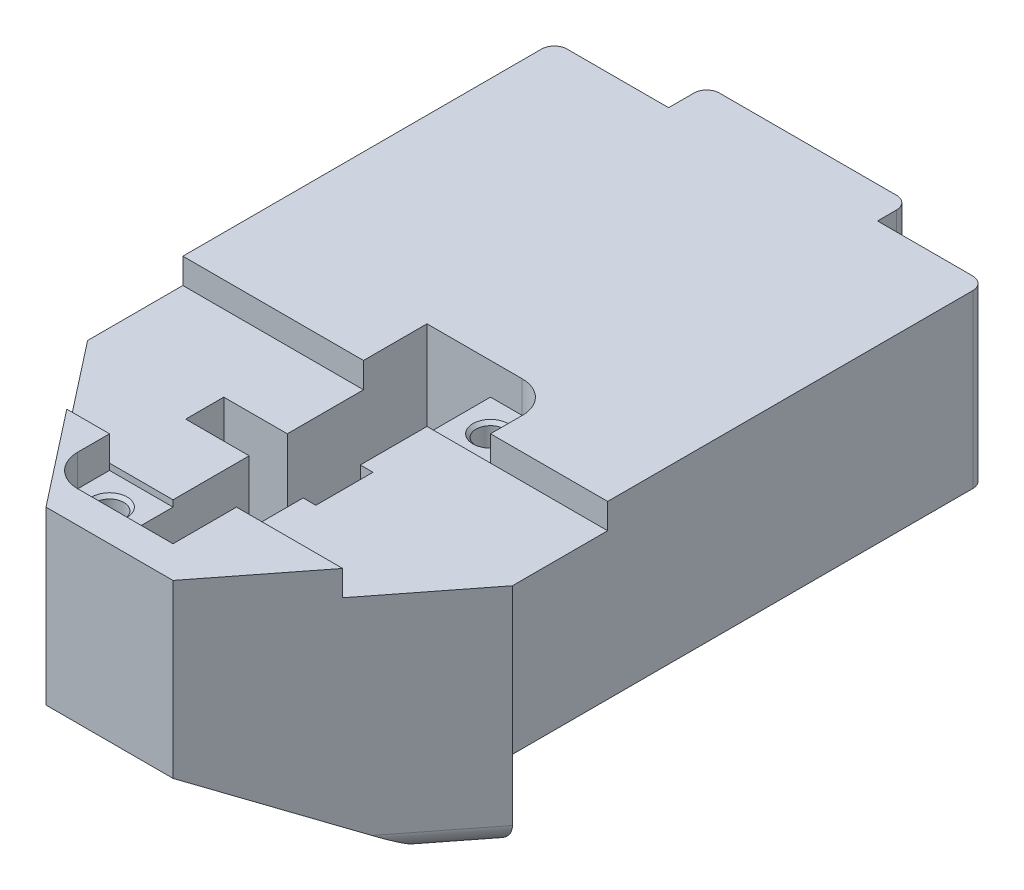
SolidWorks part; units mm, degrees
ref_plane "Front Plane" through (0, 0, 0) normal (0, 0, 1) x (1, 0, 0)
ref_plane "Top Plane" through (0, 0, 0) normal (0, 1, 0) x (1, 0, 0)
ref_plane "Right Plane" through (0, 0, 0) normal (1, 0, 0) x (0, 0, -1)
sketch "Sketch1" plane through (0, 0, 0) normal (0, 1, 0) x (1, 0, 0)
  line L0 (0, 0) -> (-16.35, 0)
  line L1 (-16.35, 0) -> (-16.35, -9.85)
  line L2 (-16.35, -9.85) -> (-2.6, -9.85)
  line L3 (-20.1, -33) -> (-20.1, -75)
  line L4 (-20.1, -75) -> (0, -75)
  line L5 (0, -75) -> (0, 0)
  line L6 (-2.6, -9.85) -> (-2.6, -33)
  line L7 (-2.6, -33) -> (-20.1, -33)
  dimension "D1" = 16.35
  dimension "D2" = 9.85
  dimension "D3" = 13.75
  dimension "D4" = 3.75
  dimension "D5" = 23.15
  dimension "D6" = 42
extrude "Boss-Extrude1" add sketch "Sketch1" along normal blind 7.7
sketch "Sketch2" plane through (0, 0, 75) normal (0, 0, 1) x (1, 0, 0)
  line L0 (-20.1, 7.7) -> (-20.1, 0) construction
  line L1 (-20.1, 5.1) -> (-13.1, 5.1)
  line L2 (-20.1, 5.1) -> (-20.1, 2)
  line L3 (-20.1, 2) -> (-13.1, 2)
  line L4 (-13.1, 5.1) -> (-13.1, 2)
  line L5 (-20.1, 0) -> (0, 0) construction
  dimension "D1" = 7
  dimension "D2" = 3.1
  dimension "D3" = 2
extrude "Cut-Extrude1" cut sketch "Sketch2" against normal through all
fillet "Fillet1" radius 10 1 edges at (-2.6, 3.85, 33)
sketch "Sketch3" plane through (0, 7.7, 0) normal (0, 1, 0) x (1, 0, 0)
  line L0 (0, 0) -> (0, -75)
  line L1 (0, -75) -> (-33.45, -75)
  line L2 (-33.45, -75) -> (-33.45, 0)
  line L3 (-33.45, 0) -> (0, 0)
  line L4 (0, -75) -> (0, -105)
  line L5 (0, -105) -> (-10, -105)
  line L6 (0, 0) -> (0, 4.5)
  line L7 (-33.45, -75) -> (-10, -105)
  line L8 (0, 4.5) -> (-33.45, 4.5)
  line L9 (-33.45, 4.5) -> (-33.45, 0)
  line M7 (0, -75) -> (0, 0)
  line M8 (0, 0) -> (-16.35, 0)
  line M9 (-16.35, 0) -> (-16.35, -9.85)
  line M10 (-16.35, -9.85) -> (-2.6, -9.85)
  line M11 (-2.6, -9.85) -> (-2.6, -23)
  arc M12 (-2.6, -23) -> (-12.6, -33) centre (-12.6, -23) cw
  line M13 (-12.6, -33) -> (-20.1, -33)
  line M14 (-20.1, -33) -> (-20.1, -75)
  line M15 (-20.1, -75) -> (0, -75)
  dimension "D1" = 33.45
  dimension "D2" = 30
  dimension "D3" = 10
  dimension "D4" = 4.5
extrude "Boss-Extrude2" add sketch "Sketch3" along normal blind 2 contours M15 M7 M8 M9 M10 M11 M12 M13 M14 | L3 L2 L1 M14 M13 M12 M11 M10 M9 | L5 L4 L1 M15 | L3 M8 region at (-9.1846, 7.7, 44.4658) region at (-16.725, 7.7, -2.25) region at (-11.9172, 7.7, 87.3015) region at (-22.489, 7.7, 32.1752)
sketch "Sketch4" plane through (0, 0, 0) normal (1, 0, 0) x (0, 0, -1)
  line L0 (-105, 9.7) -> (-105, 34.7)
  line L1 (-105, 34.7) -> (4.5, 34.7)
  line L4 (-105, 9.7) -> (4.5, 9.7)
  line L5 (4.5, 9.7) -> (4.5, 34.7)
  dimension "D2" = 25
extrude "Boss-Extrude3" add sketch "Sketch4" against normal up to surface (33.45 mm away) up to face at (-33.45, 8.7, 35.25)
sketch "Sketch5" plane through (-33.45, 0, 0) normal (-1, 0, 0) x (0, 0, 1)
  line L0 (75, 7.7) -> (75, -5)
  line L1 (75, -5) -> (82, -5)
  line L2 (82, -5) -> (105, 7.7)
  line L3 (105, 7.7) -> (75, 7.7)
  line L4 (33, 0) -> (75, 0) construction
  dimension "D1" = 5
  dimension "D2" = 7
extrude "Boss-Extrude4" add sketch "Sketch5" against normal up to surface (33.45 mm away) up to face at (0, 12.525, 43.875)
sketch "Sketch6" plane through (0, 7.7, 0) normal (0, 1, 0) x (1, 0, 0)
  line L0 (-33.45, -75) -> (-10, -105)
  line L1 (-10, -105) -> (-33.45, -105)
  line L2 (-33.45, -105) -> (-33.45, -75)
extrude "Cut-Extrude2" cut sketch "Sketch6" against normal through all both and the other way through all
sketch "Sketch7" plane through (0, 0, 0) normal (1, 0, 0) x (0, 0, -1)
  line L0 (-75, 0) -> (-85, 0)
  line L1 (-85, 0) -> (-80, -5)
  line L2 (-82, -5) -> (-75, -5) construction
  line L3 (-80, -5) -> (-75, -5)
  line L4 (-75, -5) -> (-75, 0)
  dimension "D1" = 5
  dimension "D2" = 10
extrude "Cut-Extrude3" cut sketch "Sketch7" against normal blind 10
fillet "Fillet3" radius 1 2 edges at (-5, -5, 80) (-10, -5, 77.5)
fillet "Fillet4" [suppressed] radius 5
sketch "Sketch9" plane through (0, 0, 0) normal (1, 0, 0) x (0, 0, -1)
  line L4 (4.5, 34.7) -> (-105, 34.7) construction
  line L5 (-90, 34.7) -> (-60, 34.7)
  line L6 (-90, 34.7) -> (-90, 30.7)
  line L7 (-90, 30.7) -> (-60, 30.7)
  line L8 (-60, 34.7) -> (-60, 30.7)
  line L9 (-105, 34.7) -> (-105, 7.7) construction
  dimension "D1" = 4
  dimension "D2" = 30
  dimension "D3" = 15
extrude "Cut-Extrude5" cut sketch "Sketch9" against normal up to next
mirror "Mirror1" about plane through (0, 7.7, 75) normal (-1, 0, 0) of bodies 113 110
fillet "Fillet5" radius 3 2 edges at (-30.7142, -5, 78.5) (30.7142, -5, 78.5)
sketch "Sketch8" plane through (0, 34.7, 0) normal (0, 1, 0) x (1, 0, 0)
  line L0 (33.45, 4.5) -> (33.45, -0.5)
  line L2 (33.45, -0.5) -> (16.45, -0.5)
  line L3 (16.45, -0.5) -> (16.45, 4.5)
  line L5 (16.45, 4.5) -> (33.45, 4.5)
  line L6 (0, 37.0905) -> (0, -37.0905) construction
  line L7 (-16.45, -0.5) -> (-16.45, 4.5) construction
  line L8 (-33.45, -0.5) -> (-16.45, -0.5) construction
  line L9 (-33.45, 4.5) -> (-33.45, -0.5) construction
  line L10 (-16.45, 4.5) -> (-33.45, 4.5) construction
  line L11 (-15.45, -1.5) -> (-15.45, 5.5)
  line L12 (-15.45, 5.5) -> (-34.45, 5.5)
  line L13 (-34.45, 5.5) -> (-34.45, -1.5)
  line L14 (-34.45, -1.5) -> (-15.45, -1.5)
  line L15 (33.45, 4.5) -> (33.45, -60) construction
  point P2 (33.45, 4.5)
  point P3 (33.45, -0.5)
  point P13 (0, 0)
  dimension "D1" = 5
  dimension "D2" = 17
  dimension "D3" = 1
extrude "Cut-Extrude4" cut sketch "Sketch8" against normal up to surface (34.7 mm away) up to face at (0, 0, 38.419)
fillet "Fillet6" radius 2 2 edges at (-15.45, 21.2, -4.5) (-33.45, 21.2, 1.5)
fillet "Fillet7" radius 2 2 edges at (33.45, 21.2, 0.5) (16.45, 21.2, -4.5)
sketch "Sketch11" plane through (0, 34.7, 0) normal (0, 1, 0) x (1, 0, 0)
  line L0 (0, -90) -> (0, -60) construction
  line L1 (-5, -100) -> (5, -100)
  line L2 (-5, -100) -> (-5, -50)
  line L3 (-5, -50) -> (5, -50)
  line L4 (5, -100) -> (5, -50)
  line L5 (-5, -100) -> (5, -50) construction
  line L6 (-5, -50) -> (5, -100) construction
  line L7 (-21.725, -90) -> (21.725, -90) construction
  line L8 (-33.45, -60) -> (33.45, -60) construction
  line L9 (-33.45, -60) -> (33.45, -60) construction
  line L14 (5, -50) -> (10, -50)
  line L15 (5, -50) -> (5, -60)
  line L16 (5, -60) -> (15, -60)
  line L17 (15, -55) -> (15, -60)
  line L19 (-5, -100) -> (-10, -100)
  line L20 (-5, -100) -> (-5, -90)
  line L21 (-5, -90) -> (-15, -90)
  line L22 (-15, -95) -> (-15, -90)
  arc A0 (10, -50) -> (15, -55) centre (10, -55) cw
  arc A1 (-10, -100) -> (-15, -95) centre (-10, -95) cw
  point P0 (0, -75)
  point P11 (0, -75)
  point P12 (0, -75)
  line M12 (-33.45, -60) -> (33.45, -60)
  dimension "D4" = 5
  dimension "D1" = 50
  dimension "D2" = 10
  dimension "D3" = 10
extrude "Cut-Extrude6" cut sketch "Sketch11" against normal blind 22 contours L1 L4 L2 M12 | L4 L3 L2 M12 region at (0, 34.7, 80) region at (0, 34.7, 55)
extrude "Cut-Extrude9" cut sketch "Sketch11<3>" against normal blind 5 contours L17 L4 | L17 L2 region at (-9.7799, 34.7, 94.7799) region at (9.7799, 34.7, 55.2201)
sketch "Sketch11<3>" plane through (0, 34.7, 0) normal (0, 1, 0) x (1, 0, 0) same geometry as "Sketch11"
sketch "Sketch12" plane through (0, 29.7, 0) normal (0, 1, 0) x (1, 0, 0)
  circle A0 centre (10, -55) radius 2.275
  circle A2 centre (-10, -95) radius 2.275
  arc A3 (15, -55) -> (10, -50) centre (10, -55) ccw construction
  arc A4 (-15, -95) -> (-10, -100) centre (-10, -95) ccw construction
  point P5 (9.8011, -75)
  point P7 (0, 0)
  point P16 (0, 0)
  point P17 (0, 0)
  dimension "D1" = 4.55
extrude "Cut-Extrude7" cut sketch "Sketch12" against normal blind 8
chamfer "Chamfer1" distance 0.5 angle 45 2 edges at (10, 29.7, 57.275) (-10, 29.7, 92.725)
sketch "Sketch13" plane through (0, 30.7, 0) normal (0, 1, 0) x (1, 0, 0)
  line L0 (-5, -75) -> (5, -75) construction
  line L3 (-5, -100) -> (-5, -50) construction
  line L8 (5, -60) -> (5, -90) construction
  line L9 (5, -100) -> (5, -50) construction
  line L10 (5, -70.5) -> (7, -70.5)
  line L11 (5, -70.5) -> (5, -79.5)
  line L12 (5, -79.5) -> (7, -79.5)
  line L13 (7, -70.5) -> (7, -79.5)
  line L14 (-5, -60) -> (-5, -90) construction
  line L15 (-5, -72) -> (-15, -72)
  line L16 (-5, -72) -> (-5, -78)
  line L17 (-5, -78) -> (-15, -78)
  line L18 (-15, -72) -> (-15, -78)
  point P12 (5, -75)
  point P19 (-5, -75)
  dimension "D1" = 9
  dimension "D2" = 2
  dimension "D3" = 6
  dimension "D4" = 10
extrude "Cut-Extrude10" cut sketch "Sketch13" against normal up to surface (18 mm away) up to face at (0, 12.7, 75)
